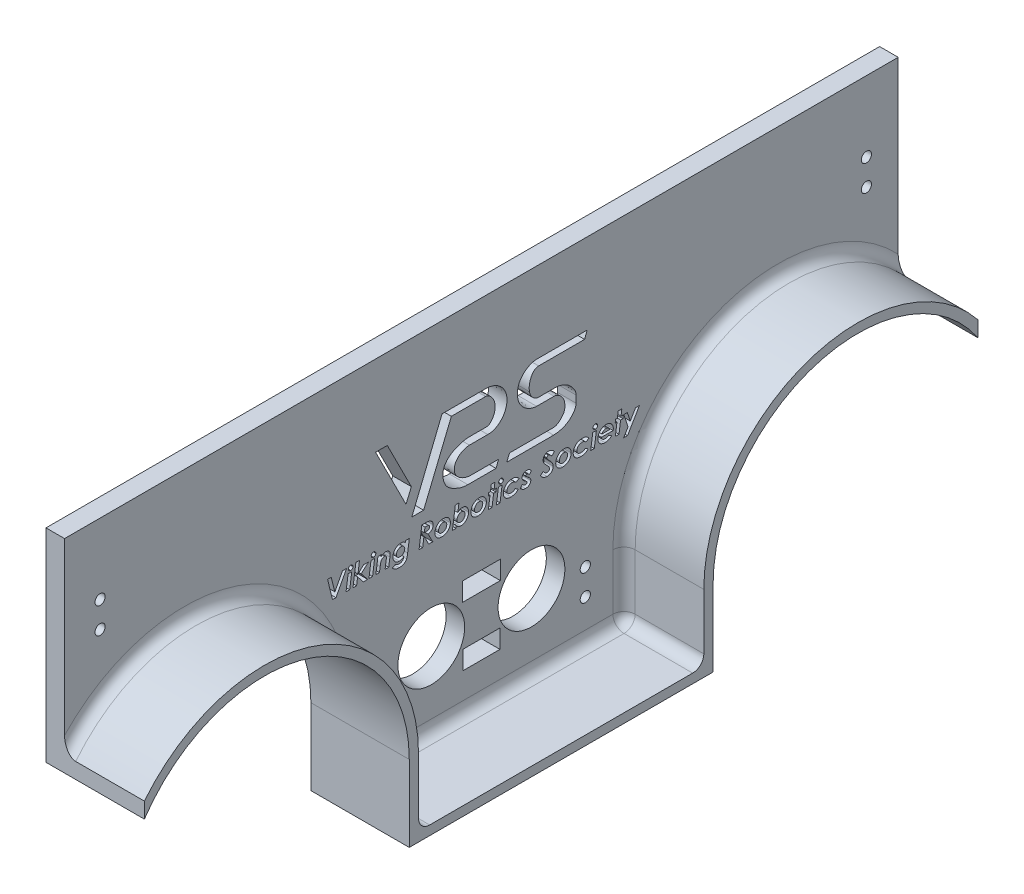
SolidWorks part; units mm, degrees
ref_plane "Front" through (0, 0, 0) normal (0, 0, 1) x (1, 0, 0)
ref_plane "Top" through (0, 0, 0) normal (0, 1, 0) x (1, 0, 0)
ref_plane "Right" through (0, 0, 0) normal (1, 0, 0) x (0, 0, -1)
sketch "wheelArchesSketch" plane through (0, 0, 0) normal (1, 0, 0) x (0, 0, -1)
  line L0 (112.295, 7.5) -> (112.295, 0) construction
  line L1 (0, 0) -> (224.59, 0) construction
  line L2 (0, 0) -> (0, 7.5) construction
  line L3 (0, 7.5) -> (224.59, 7.5) construction
  line L4 (224.59, 0) -> (224.59, 7.5) construction
  line L5 (71.3676, 20.5282) -> (71.3676, 0)
  line L6 (153.2224, 20.5282) -> (153.2224, 0)
  line L7 (73.8676, 20.5282) -> (73.8676, 0)
  line L8 (0, 42.2846) -> (0, 46.5011)
  line L9 (150.7224, 20.5282) -> (150.7224, 0)
  line L10 (224.59, 42.2846) -> (224.59, 46.5011)
  line L12 (150.7224, 0) -> (153.2224, 0)
  line L13 (71.3676, 0) -> (73.8676, 0)
  arc A1 (0, 42.2846) -> (71.3676, 20.5282) centre (32.3676, 20.5282) cw
  arc A2 (224.59, 42.2846) -> (153.2224, 20.5282) centre (192.2224, 20.5282) ccw
  arc A3 (0, 46.5011) -> (73.8676, 20.5282) centre (32.3676, 20.5282) cw
  arc A4 (-2.0748, 43.6792) -> (73.8676, 20.5282) centre (32.3676, 20.5282) cw construction
  arc A5 (224.59, 46.5011) -> (150.7224, 20.5282) centre (192.2224, 20.5282) ccw
  point P5 (32.3676, 20.5282)
  dimension "D5" = 39
  dimension "D1" = 224.59
  dimension "D2" = 7.5
  dimension "D3" = 32.3676
  dimension "D4" = 13.0282
  dimension "D6" = 2.5
extrude "wheelArches" add sketch "wheelArchesSketch" along normal blind 26.5
sketch "Sketch3" plane through (0, 0, 0) normal (1, 0, 0) x (0, 0, -1)
  line L0 (0, 46.5011) -> (0, 42.2846) construction
  line L1 (71.3676, 0) -> (153.2224, 0)
  line L2 (0, 42.2846) -> (0, 87)
  line L3 (0, 87) -> (224.59, 87)
  line L4 (224.59, 42.2846) -> (224.59, 87)
  line L6 (224.59, 42.2846) -> (224.59, 46.5011) construction
  line L7 (71.3676, 0) -> (73.8676, 0) construction
  line L8 (71.3676, 20.5282) -> (71.3676, 0) construction
  line L9 (71.3676, 20.5282) -> (71.3676, 0)
  line L10 (153.2224, 0) -> (153.2224, 20.5282) construction
  line L11 (153.2224, 0) -> (153.2224, 20.5282)
  arc A0 (71.3676, 20.5282) -> (0, 42.2846) centre (32.3676, 20.5282) ccw construction
  arc A1 (71.3676, 20.5282) -> (0, 42.2846) centre (32.3676, 20.5282) ccw
  arc A2 (224.59, 42.2846) -> (153.2224, 20.5282) centre (192.2224, 20.5282) ccw construction
  arc A3 (224.59, 42.2846) -> (153.2224, 20.5282) centre (192.2224, 20.5282) ccw
  dimension "D1" = 87
extrude "sideWall" add sketch "Sketch3" along normal blind 2.5
sketch "Sketch4" plane through (2.5, 0, 0) normal (1, 0, 0) x (0, 0, -1)
  line L0 (150.7224, 0) -> (150.7224, 20.5282) construction
  line L1 (73.8676, 0) -> (150.7224, 0) construction
  line L2 (73.8676, 0) -> (73.8676, 7.5) construction
  line L3 (73.8676, 7.5) -> (150.7224, 7.5) construction
  line L4 (150.7224, 0) -> (150.7224, 7.5) construction
  line L5 (112.295, 7.5) -> (112.295, 37) construction
  line L6 (87.295, 7.5) -> (137.295, 7.5) construction
  line L7 (87.295, 7.5) -> (87.295, 37) construction
  line L8 (87.295, 37) -> (137.295, 37) construction
  line L9 (137.295, 7.5) -> (137.295, 37) construction
  circle A0 centre (98.795, 22.5) radius 9
  circle A1 centre (90.9643, 31.289) radius 0.875
  circle A2 centre (90.9643, 13.711) radius 0.875
  circle A3 centre (133.6257, 13.711) radius 0.875
  circle A4 centre (133.6257, 31.289) radius 0.875
  circle A5 centre (125.795, 22.5) radius 9
  point P11 (112.295, 7.5)
  point P12 (112.295, 7.5)
  dimension "D4" = 18
  dimension "D7" = 1.75
  dimension "D1" = 7.5
  dimension "D2" = 29.5
  dimension "D3" = 50
  dimension "D5" = 5.711
  dimension "D6" = 3.6693
  dimension "D8" = 6.211
  dimension "D9" = 3.6693
  dimension "D10" = 15
  dimension "D11" = 11.5
extrude "distanceSensorMountingHoles1" cut sketch "Sketch4" against normal blind 10
sketch "Sketch5" plane through (2.5, 0, 0) normal (1, 0, 0) x (0, 0, -1)
  circle A0 centre (90.9643, 31.289) radius 1.25
  circle A1 centre (90.9643, 13.711) radius 1.25
  circle A2 centre (133.6257, 13.711) radius 1.25
  circle A3 centre (133.6257, 31.289) radius 1.25
  dimension "D1" = 2.5
extrude "distanceSensorMountingHoles2" cut sketch "Sketch5" against normal offset from surface (1.5 mm away) 1 up to face at (0, 31.289, -90.0893)
sketch "Sketch6" plane through (0, 87, 0) normal (0, 1, 0) x (1, 0, 0)
  line L4 (0, 224.59) -> (0, 0)
  line L5 (0, 0) -> (2.5, 0)
  line L6 (2.5, 0) -> (2.5, 224.59)
  line L7 (2.5, 224.59) -> (0, 224.59)
  line L8 (0, 224.59) -> (0, 0)
  line L9 (0, 0) -> (2.5, 0)
  line L10 (2.5, 0) -> (2.5, 224.59)
  line L11 (2.5, 224.59) -> (0, 224.59)
  dimension "D1" = 0
extrude "wallExtension" add sketch "Sketch6" along normal blind 5
ref_plane "referencePlane1" through (0, 87, 0) normal (0, 1, 0) x (1, 0, 0)
sketch "Sketch7" plane through (0, 87, 0) normal (0, 1, 0) x (1, 0, 0)
  line L0 (0, 112.295) -> (-12.5, 112.295) construction
  line L1 (0, 224.59) -> (0, 0) construction
  line L2 (0, 207.455) -> (-12.5, 207.455)
  line L3 (0, 0) -> (-12.5, 0)
  line L4 (0, 0) -> (0, 17.135)
  line L5 (0, 17.135) -> (-12.5, 17.135)
  line L6 (-12.5, 0) -> (-12.5, 17.135)
  line L7 (-12.5, 224.59) -> (-12.5, 207.455)
  line L8 (0, 224.59) -> (-12.5, 224.59)
  line L9 (0, 224.59) -> (0, 207.455)
  dimension "D1" = 17.135
  dimension "D2" = 12.5
extrude "topChassisMountingTabs" add sketch "Sketch7" against normal blind 5
sketch "Sketch8" plane through (0, 87, 0) normal (0, 1, 0) x (1, 0, 0)
  line L0 (0, 112.295) -> (-12.8293, 112.295) construction
  line L1 (0, 224.59) -> (0, 0) construction
  line L2 (-6.25, 0) -> (-6.25, 17.135) construction
  line L3 (-12.5, 0) -> (0, 0) construction
  line L4 (0, 17.135) -> (-12.5, 17.135) construction
  circle A0 centre (-6.25, 8.5675) radius 1.375
  circle A1 centre (-6.25, 216.0225) radius 1.375
  dimension "D1" = 2.75
extrude "topChassisMountingHoles" cut sketch "Sketch8" against normal blind 5
ref_plane "referencePlane2" through (0, 7.5, 0) normal (0, -1, 0) x (-1, 0, 0)
sketch "Sketch9" plane through (0, 7.5, 0) normal (0, -1, 0) x (-1, 0, 0)
  line L0 (0, 224.59) -> (0, 0) construction
  line L1 (0, 87.295) -> (12.5, 87.295)
  line L2 (0, 87.295) -> (0, 137.295)
  line L3 (0, 137.295) -> (12.5, 137.295)
  line L4 (12.5, 87.295) -> (12.5, 137.295)
  point P4 (0, 112.295)
  point P7 (0, 112.295)
  dimension "D1" = 12.5
  dimension "D2" = 50
extrude "bottomTab" add sketch "Sketch9" against normal blind 1.75
sketch "Sketch10" plane through (0, 9.25, 0) normal (0, 1, 0) x (1, 0, 0)
  line L0 (-12.5, 112.295) -> (0, 112.295) construction
  line L1 (-12.5, 87.295) -> (-12.5, 137.295) construction
  line L2 (0, 137.295) -> (0, 87.295) construction
  line L3 (0, 87.295) -> (-12.5, 87.295) construction
  circle A0 centre (-9.75, 90.295) radius 1.375
  circle A1 centre (-9.75, 134.295) radius 1.375
  dimension "D1" = 2.75
  dimension "D2" = 3
  dimension "D3" = 2.75
extrude "bottomTabMountingHoles" cut sketch "Sketch10" against normal blind 1.75
sketch "Sketch11" plane through (0, 92, 0) normal (0, 1, 0) x (1, 0, 0)
  line L4 (2.5, 224.59) -> (0, 224.59)
  line L5 (0, 224.59) -> (0, 0)
  line L6 (0, 0) -> (2.5, 0)
  line L7 (2.5, 0) -> (2.5, 224.59)
  line L8 (2.5, 224.59) -> (0, 224.59)
  line L9 (0, 224.59) -> (0, 0)
  line L10 (0, 0) -> (2.5, 0)
  line L11 (2.5, 0) -> (2.5, 224.59)
  dimension "D1" = 0
extrude "Boss-Extrude1" add sketch "Sketch11" along normal blind 5
sketch "Sketch12" plane through (2.5, 0, 0) normal (1, 0, 0) x (0, 0, -1)
  line L6 (150.7224, 0) -> (150.7224, 20.5282)
  line L7 (224.59, 46.5011) -> (224.59, 97)
  line L8 (224.59, 97) -> (0, 97)
  line L9 (0, 97) -> (0, 46.5011)
  line L10 (73.8676, 20.5282) -> (73.8676, 0)
  line L11 (73.8676, 0) -> (150.7224, 0)
  line L12 (150.7224, 0) -> (150.7224, 20.5282)
  line L13 (224.59, 46.5011) -> (224.59, 97)
  line L14 (224.59, 97) -> (0, 97)
  line L15 (0, 97) -> (0, 46.5011)
  line L16 (73.8676, 20.5282) -> (73.8676, 0)
  line L17 (73.8676, 0) -> (150.7224, 0)
  circle A0 centre (90.9643, 13.711) radius 0.875 construction
  circle A1 centre (133.6257, 13.711) radius 0.875 construction
  arc A2 (224.59, 46.5011) -> (150.7224, 20.5282) centre (192.2224, 20.5282) ccw
  arc A3 (73.8676, 20.5282) -> (0, 46.5011) centre (32.3676, 20.5282) ccw
  arc A4 (224.59, 46.5011) -> (150.7224, 20.5282) centre (192.2224, 20.5282) ccw
  arc A5 (73.8676, 20.5282) -> (0, 46.5011) centre (32.3676, 20.5282) ccw
  circle A6 centre (133.6257, 31.289) radius 0.875 construction
  circle A7 centre (90.9643, 31.289) radius 0.875 construction
  circle A8 centre (90.9643, 13.711) radius 0.875
  circle A9 centre (133.6257, 13.711) radius 0.875
  circle A10 centre (133.6257, 31.289) radius 0.875
  circle A11 centre (90.9643, 31.289) radius 0.875
  dimension "D1" = 0
extrude "Boss-Extrude2" add sketch "Sketch12" along normal blind 2.5
sketch "Sketch13" plane through (1, 0, 0) normal (1, 0, 0) x (0, 0, -1)
  circle A0 centre (90.9643, 31.289) radius 1.25 construction
  circle A1 centre (90.9643, 31.289) radius 1.25
  circle A2 centre (133.6257, 13.711) radius 1.25 construction
  circle A3 centre (133.6257, 13.711) radius 1.25
  circle A4 centre (90.9643, 13.711) radius 1.25 construction
  circle A5 centre (90.9643, 13.711) radius 1.25
  circle A6 centre (133.6257, 31.289) radius 1.25 construction
  circle A7 centre (133.6257, 31.289) radius 1.25
extrude "Cut-Extrude1" cut sketch "Sketch13" along normal through all
sketch "Sketch14" plane through (2.5, 0, 0) normal (-1, 0, 0) x (0, 0, 1)
  circle A1 centre (-125.795, 22.5) radius 9
  circle A2 centre (-125.795, 22.5) radius 9
  circle A3 centre (-98.795, 22.5) radius 9
  circle A4 centre (-98.795, 22.5) radius 9
  dimension "D1" = 0
  dimension "D2" = 0
extrude "Cut-Extrude2" cut sketch "Sketch14" against normal blind 10
sketch "Sketch15" plane through (5, 0, 0) normal (1, 0, 0) x (0, 0, -1)
  line L0 (98.795, 13.5) -> (98.795, 31.5) construction
  line L1 (89.795, 22.5) -> (107.795, 22.5) construction
  line L3 (107.295, 17.5) -> (117.295, 17.5)
  line L4 (107.295, 17.5) -> (107.295, 12.5)
  line L5 (107.295, 12.5) -> (117.295, 12.5)
  line L6 (117.295, 17.5) -> (117.295, 12.5)
  line L7 (107.185, 33.5) -> (117.405, 33.5)
  line L8 (107.185, 33.5) -> (107.185, 28.5)
  line L9 (107.185, 28.5) -> (117.405, 28.5)
  line L10 (117.405, 33.5) -> (117.405, 28.5)
  circle A0 centre (98.795, 22.5) radius 9 construction
  circle A1 centre (98.795, 22.5) radius 9 construction
  point P24 (107.185, 31)
  dimension "D1" = 5
  dimension "D2" = 10
  dimension "D3" = 8.5
  dimension "D4" = 5
  dimension "D5" = 5
  dimension "D6" = 10.22
  dimension "D7" = 8.39
  dimension "D8" = 8.5
extrude "Cut-Extrude3" cut sketch "Sketch15" against normal blind 10
sketch "Sketch16" plane through (0, 87, 0) normal (0, 1, 0) x (1, 0, 0)
  line L0 (0, 224.59) -> (0, 0) construction
  line L1 (-12.5, 0) -> (0, 0)
  line L2 (-12.5, 0) -> (-12.5, 2)
  line L3 (-12.5, 2) -> (0, 2)
  line L4 (0, 0) -> (0, 2)
  dimension "D1" = 2
extrude "Cut-Extrude4" cut sketch "Sketch16" against normal blind 10
sketch "Sketch17" plane through (5, 0, 0) normal (1, 0, 0) x (0, 0, -1)
  line L0 (150.7224, 20.5282) -> (150.7224, 0) construction
  line L1 (73.8676, 0) -> (150.7224, 0)
  line L2 (73.8676, 0) -> (73.8676, 2.5)
  line L3 (73.8676, 2.5) -> (150.7224, 2.5)
  line L4 (150.7224, 0) -> (150.7224, 2.5)
  dimension "D1" = 2.5
extrude "Boss-Extrude3" add sketch "Sketch17" along normal up to surface (21.5 mm away) up to face at (26.5, 30.4055, -51.2877)
fillet "Fillet1" radius 3 7 edges at (5, 11.5141, -150.7224) (5, 11.5141, -73.8676) (5, 59.6786, -178.4566) (5, 2.5, -112.295) (5, 59.6786, -46.1334) (15.75, 2.5, -150.7224) (15.75, 2.5, -73.8676)
sketch "Sketch18" plane through (0, 0, 0) normal (-1, 0, 0) x (0, 0, 1)
  line L0 (-112.295, 0) -> (-112.295, 97) construction
  line L5 (0, 97) -> (0, 42.2846) construction
  line L6 (-224.59, 51.0665) -> (-224.59, 97) construction
  line L11 (-71.3676, 0) -> (-153.2224, 0) construction
  line L12 (-224.59, 97) -> (0, 97) construction
  line L14 (-208.455, 82) -> (-223.59, 82) construction
  line L15 (-208.455, 82) -> (-208.455, 67) construction
  line L16 (-208.455, 67) -> (-223.59, 67) construction
  line L17 (-223.59, 82) -> (-223.59, 67) construction
  line L19 (-17.135, 82) -> (-2, 82) construction
  line L20 (-17.135, 82) -> (-17.135, 67) construction
  line L21 (-17.135, 67) -> (-2, 67) construction
  line L22 (-2, 82) -> (-2, 67) construction
  circle A6 centre (-216.0225, 78) radius 1.375
  circle A7 centre (-216.0225, 71) radius 1.375
  circle A8 centre (-9.5675, 78) radius 1.375
  circle A9 centre (-9.5675, 71) radius 1.375
  point P11 (-216.0225, 82)
  point P14 (-9.5675, 82)
  dimension "D2" = 1
  dimension "D7" = 4
  dimension "D5" = 2.75
  dimension "D1" = 15.135
  dimension "D3" = 15
  dimension "D4" = 15
  dimension "D6" = 7
  dimension "D8" = 7
  dimension "D9" = 4
  dimension "D10" = 2
extrude "Cut-Extrude5" cut sketch "Sketch18" against normal blind 10
sketch "Sketch19" plane through (0, 87, 0) normal (0, 1, 0) x (1, 0, 0)
  line L1 (-12.5, 17.135) -> (0, 17.135)
  line L2 (-12.5, 17.135) -> (-12.5, 2)
  line L3 (-12.5, 2) -> (0, 2)
  line L4 (0, 17.135) -> (0, 2)
  line L5 (-12.5, 224.59) -> (0, 224.59)
  line L6 (-12.5, 224.59) -> (-12.5, 207.455)
  line L7 (-12.5, 207.455) -> (0, 207.455)
  line L8 (0, 224.59) -> (0, 207.455)
extrude "Cut-Extrude6" cut sketch "Sketch19" against normal blind 10
sketch "Sketch20" plane through (0, 0, 0) normal (-1, 0, 0) x (0, 0, 1)
  line L0 (-112.295, 9.25) -> (-112.295, 33.5) construction
  line L1 (-137.295, 9.25) -> (-87.295, 9.25) construction
  line L2 (-107.185, 33.5) -> (-117.405, 33.5) construction
  circle A0 centre (-140.295, 20.25) radius 1.375
  circle A1 centre (-140.295, 13.25) radius 1.375
  circle A2 centre (-84.295, 13.25) radius 1.375
  circle A3 centre (-84.295, 20.25) radius 1.375
  dimension "D1" = 2.75
  dimension "D2" = 7
  dimension "D3" = 3
  dimension "D4" = 4
extrude "Cut-Extrude7" cut sketch "Sketch20" against normal blind 10
sketch "Sketch21" plane through (0, 9.25, 0) normal (0, 1, 0) x (1, 0, 0)
  line L4 (0, 87.295) -> (0, 137.295)
  line L5 (0, 137.295) -> (-12.5, 137.295)
  line L6 (-12.5, 137.295) -> (-12.5, 87.295)
  line L7 (-12.5, 87.295) -> (0, 87.295)
  line L8 (0, 87.295) -> (0, 137.295)
  line L9 (0, 137.295) -> (-12.5, 137.295)
  line L10 (-12.5, 137.295) -> (-12.5, 87.295)
  line L11 (-12.5, 87.295) -> (0, 87.295)
  dimension "D1" = 0
extrude "Cut-Extrude8" cut sketch "Sketch21" against normal blind 10
sketch "Sketch22" plane through (5, 0, 0) normal (1, 0, 0) x (0, 0, -1)
  circle A0 centre (90.9643, 31.289) radius 1.25
  circle A1 centre (90.9643, 13.711) radius 1.25
  circle A2 centre (133.6257, 13.711) radius 1.25
  circle A3 centre (133.6257, 31.289) radius 1.25
  circle A5 centre (90.9643, 31.289) radius 1.25 construction
  circle A6 centre (90.9643, 13.711) radius 1.25 construction
  circle A7 centre (133.6257, 31.289) radius 1.25 construction
  circle A8 centre (133.6257, 13.711) radius 1.25 construction
extrude "Boss-Extrude4" add sketch "Sketch22" against normal up to surface (5 mm away) up to face at (0, 46.5599, -112.295)
sketch "Sketch24" plane through (5, 0, 0) normal (1, 0, 0) x (0, 0, -1)
  line L0 (147.5058, 113.6649) -> (400.1724, 113.6649) construction
sketch "vrs logo sketch 1" plane through (5, 0, 0) normal (1, 0, 0) x (0, 0, -1)
  line L0 (83.795, 75.25) -> (91.9924, 58.9987)
  line L1 (83.795, 55.25) -> (140.795, 55.25) construction
  line L2 (83.795, 55.25) -> (83.795, 75.25) construction
  line L3 (83.795, 75.25) -> (140.795, 75.25) construction
  line L4 (140.795, 55.25) -> (140.795, 75.25) construction
  line L5 (91.9924, 58.9987) -> (93.4297, 62.4001)
  line L6 (93.4297, 62.4001) -> (86.948, 75.25)
  line L7 (83.795, 75.25) -> (86.948, 75.25)
  line L8 (93.5622, 55.25) -> (101.6971, 75.25)
  line L9 (93.5622, 55.25) -> (96.7347, 55.25)
  line L10 (96.7347, 55.25) -> (104.2097, 73.4229)
  line L11 (104.2097, 73.4229) -> (113.4267, 73.4229)
  line L12 (101.6971, 75.25) -> (113.4267, 75.25)
  line L14 (113.6549, 66.2225) -> (109.0786, 66.2225)
  line L15 (108.649, 55.25) -> (116.2406, 55.25)
  line L16 (116.2406, 55.25) -> (116.9169, 57.0415)
  line L17 (116.9169, 57.0415) -> (109.3254, 57.0415)
  line L18 (109.0786, 64.2665) -> (114.0207, 64.2665)
  line L19 (119.112, 55.25) -> (119.8911, 57.0415)
  line L20 (119.8911, 57.0415) -> (131.7476, 57.0415)
  line L21 (119.112, 55.25) -> (131.7476, 55.25)
  line L22 (127.1813, 64.2665) -> (131.882, 64.2665)
  line L23 (137.7903, 59.7038) -> (137.7903, 61.5921)
  line L24 (131.882, 66.1231) -> (127.6113, 66.1231)
  line L25 (127.1813, 75.25) -> (140.795, 75.25)
  line L26 (140.795, 75.25) -> (140.1067, 73.4229)
  line L27 (140.1067, 73.4229) -> (127.7258, 73.4229)
  line L28 (224.59, 97) -> (0, 97) construction
  line L29 (112.295, 33.5) -> (112.295, 97) construction
  line L30 (117.405, 33.5) -> (107.185, 33.5) construction
  spline S0 degree 3 poles (113.4267, 73.4229) (113.9525, 73.4229) (115.0028, 72.7273) (116.0805, 70.9166) (116.0595, 68.7609) (115.3054, 67.2973) (114.5742, 66.4875) (113.9987, 66.2225) (113.6549, 66.2225) knots 0 0 0 0 0.157632 0.37711 0.656481 0.801127 0.898936 1 1 1 1
  spline S1 degree 3 poles (131.7476, 57.0415) (132.4242, 57.0415) (133.7383, 57.9339) (134.7873, 59.3816) (134.8085, 60.9137) (134.634, 62.1622) (133.709, 63.5128) (132.6421, 64.2665) (131.882, 64.2665) knots 0 0 0 0 0.216224 0.409178 0.515063 0.662579 0.774486 1 1 1 1
  spline S2 degree 3 poles (109.0786, 66.2225) (108.231, 66.2225) (106.3717, 65.827) (103.9189, 64.7653) (102.071, 62.8032) (101.7499, 60.0852) (102.7398, 57.4648) (104.9299, 56.1868) (106.7888, 55.4161) (108.037, 55.25) (108.649, 55.25) knots 0 0 0 0 0.134192 0.283292 0.411281 0.526526 0.689263 0.809142 0.905564 1 1 1 1
  spline S3 degree 3 poles (109.3254, 57.0415) (107.7745, 57.0815) (104.9095, 58.4278) (104.9721, 62.7864) (107.5033, 64.2156) (109.0786, 64.2665) knots 0 0 0 0 0.430007 0.587207 1 1 1 1
  spline S4 degree 3 poles (114.0207, 64.2665) (116.5078, 64.2354) (119.3744, 67.0337) (119.1976, 71.6207) (117.1158, 74.4983) (114.7913, 75.25) (113.4267, 75.25) knots 0 0 0 0 0.405476 0.592612 0.768817 1 1 1 1
  spline S5 degree 3 poles (131.7476, 55.25) (132.7169, 55.3021) (134.3226, 55.5397) (136.1797, 56.7261) (137.3685, 58.0352) (137.7903, 59.1283) (137.7903, 59.7038) knots 0 0 0 0 0.36059 0.578347 0.799146 1 1 1 1
  spline S6 degree 3 poles (137.7903, 61.5921) (137.7903, 61.8737) (137.6589, 62.6634) (136.8588, 63.8882) (135.6659, 65.0851) (134.1983, 65.8074) (133.2186, 66.0284) (132.7609, 66.0839) knots 0 0 0 0 0.113 0.331746 0.588751 0.807468 1 1 1 1
  spline S7 degree 3 poles (132.7609, 66.0839) (132.4698, 66.1192) (132.177, 66.1231) (131.882, 66.1231) knots 0 0 0 0 1 1 1 1
  spline S8 degree 3 poles (127.1813, 64.2665) (126.7197, 64.2665) (125.617, 64.5125) (124.2158, 65.2204) (122.9183, 66.5025) (122.3334, 67.5228) (122.1993, 68.257) knots 0 0 0 0 0.20352 0.489339 0.680254 1 1 1 1
  spline S9 degree 3 poles (127.6113, 66.1231) (127.3676, 66.1231) (126.867, 66.2987) (126.21, 66.7226) (125.5853, 67.4936) (125.3454, 68.1893) (125.2705, 68.6229) knots 0 0 0 0 0.204924 0.409427 0.639806 1 1 1 1
  spline S10 degree 3 poles (122.1993, 68.257) (121.9161, 69.4274) (121.9261, 71.4717) (123.3759, 73.5449) (124.7544, 74.5858) (126.0309, 75.125) (126.8446, 75.25) (127.1813, 75.25) knots 0 0 0 0 0.373666 0.579957 0.752029 0.896516 1 1 1 1
  spline S11 degree 3 poles (125.2705, 68.6229) (125.1123, 69.4156) (125.1861, 70.7682) (125.8714, 72.2737) (126.68, 73.2015) (127.3274, 73.4229) (127.7258, 73.4229) knots 0 0 0 0 0.404345 0.656951 0.820838 1 1 1 1
  point P86 (112.295, 97)
  point P88 (112.295, 75.25)
  point P96 (112.295, 65.25)
  point P97 (83.795, 65.25)
  dimension "D11" = 1.7915
  dimension "D1" = 57
  dimension "D2" = 20
  dimension "D3" = 3.7487
  dimension "D4" = 8.1974
  dimension "D5" = 1.4373
  dimension "D6" = 3.4014
  dimension "D7" = 3.1725
  dimension "D8" = 9.7672
  dimension "D9" = 17.9021
  dimension "D10" = 1.8271
  dimension "D12" = 24.854
  dimension "D13" = 3.2018
  dimension "D14" = 1.8271
  dimension "D15" = 1.9798
  dimension "D16" = 1.6669
  dimension "D17" = 5.1584
  dimension "D18" = 2.2337
  dimension "D19" = 0.9169
  dimension "D20" = 0.2396
  dimension "D21" = 2.587
  dimension "D22" = 0.0819
  dimension "D23" = 1.9243
  dimension "D24" = 1.2106
  dimension "D25" = 7.5916
  dimension "D26" = 7.5915
  dimension "D27" = 1.915
  dimension "D28" = 2.5794
  dimension "D29" = 1.1838
  dimension "D30" = 1.8883
  dimension "D31" = 2.217
  dimension "D32" = 0.3308
  dimension "D33" = 1.8913
  dimension "D34" = 1.6187
  dimension "D35" = 1.2558
  dimension "D36" = 2.614
  dimension "D37" = 1.7701
  dimension "D38" = 1.3617
  dimension "D39" = 2.571
  dimension "D40" = 0.4501
  dimension "D41" = 2.571
  dimension "D42" = 0.9042
  dimension "D43" = 4.5763
  dimension "D44" = 4.9421
  dimension "D45" = 0.8895
  dimension "D46" = 0.322
  dimension "D47" = 3.3748
  dimension "D48" = 1.3467
  dimension "D49" = 0.66
  dimension "D50" = 0.6344
  dimension "D51" = 2.7967
  dimension "D52" = 1.6292
  dimension "D53" = 1.2054
  dimension "D54" = 0.6164
  dimension "D55" = 0.145
  dimension "D56" = 3.1675
  dimension "D57" = 0.0254
  dimension "D58" = 2.6147
  dimension "D59" = 1.0653
  dimension "D60" = 1.7565
  dimension "D61" = 1.7394
  dimension "D62" = 2.4266
  dimension "D63" = 1.3285
  dimension "D64" = 9.217
  dimension "D65" = 1.9536
  dimension "D66" = 12.6356
  dimension "D67" = 11.8565
  dimension "D68" = 1.2782
  dimension "D69" = 0.1355
  dimension "D70" = 1.5916
  dimension "D71" = 0.4543
  dimension "D72" = 1.9312
  dimension "D73" = 1.0151
  dimension "D74" = 1.5049
  dimension "D75" = 0.9426
  dimension "D76" = 1.038
  dimension "D77" = 1.6472
  dimension "D78" = 1.1839
  dimension "D79" = 1.3566
  dimension "D80" = 0.0665
  dimension "D81" = 1.0663
  dimension "D82" = 0.4841
  dimension "D83" = 1.5648
  dimension "D84" = 1.4607
  dimension "D85" = 0.2862
  dimension "D86" = 1.8883
  dimension "D87" = 0.1266
  dimension "D88" = 0.808
  dimension "D89" = 0.9451
  dimension "D90" = 0.6179
  dimension "D91" = 1.3726
  dimension "D92" = 0.7891
  dimension "D93" = 1.9971
  dimension "D94" = 1.0905
  dimension "D95" = 1.2891
  dimension "D96" = 1.341
  dimension "D97" = 0.7106
  dimension "D98" = 1.4145
  dimension "D99" = 0.3115
  dimension "D100" = 1.3582
  dimension "D101" = 0.0391
  dimension "D102" = 0.8789
  dimension "D103" = 4.7007
  dimension "D104" = 4.2707
  dimension "D105" = 21.683
  dimension "D106" = 1.3625
  dimension "D107" = 0.2502
  dimension "D108" = 0.7247
  dimension "D109" = 0.1998
  dimension "D110" = 1.7247
  dimension "D111" = 0.9
  dimension "D112" = 0.4122
  dimension "D113" = 0.6268
  dimension "D114" = 0.9314
  dimension "D115" = 0.9061
  dimension "D116" = 0.6514
  dimension "D117" = 0.5384
  dimension "D118" = 1.2933
  dimension "D119" = 0.505
  dimension "D120" = 0.7628
  dimension "D121" = 0.3384
  dimension "D122" = 1.4102
  dimension "D123" = 0.1889
  dimension "D124" = 0.1124
  dimension "D125" = 0.4736
  dimension "D126" = 0.093
  dimension "D127" = 1.0443
  dimension "D128" = 0.3786
  dimension "D129" = 2.2095
  dimension "D130" = 0.2054
  dimension "D131" = 1.3574
  dimension "D132" = 1.6763
  dimension "D133" = 1.1326
  dimension "D134" = 0.6426
  dimension "D135" = 1.3694
  dimension "D136" = 1.0215
  dimension "D137" = 1.3432
  dimension "D138" = 0.5374
  dimension "D139" = 1.3111
  dimension "D140" = 0.6752
  dimension "D141" = 0.7122
  dimension "D142" = 1.0054
  dimension "D143" = 0.138
  dimension "D144" = 1.0251
  dimension "D145" = 0.3166
  dimension "D146" = 13.6137
  dimension "D147" = 12.3809
  dimension "D148" = 28.5
extrude "Cut-Extrude9" cut sketch "vrs logo sketch 1" against normal through all both and the other way through all
sketch "Sketch25" plane through (5, 0, 0) normal (1, 0, 0) x (0, 0, -1)
  line L0 (112.295, 33.5) -> (112.295, 97) construction
  line L1 (224.59, 97) -> (0, 97) construction
  line L3 (70.5049, 46.6488) -> (154.0851, 46.6488) construction
  text T0 "Viking Robotics Society" font "Century Gothic" height 5.4
  point P8 (112.295, 46.6488)
  point P13 (112.295, 46.6488)
extrude "Cut-Extrude10" cut sketch "Sketch25" against normal blind 2.5
